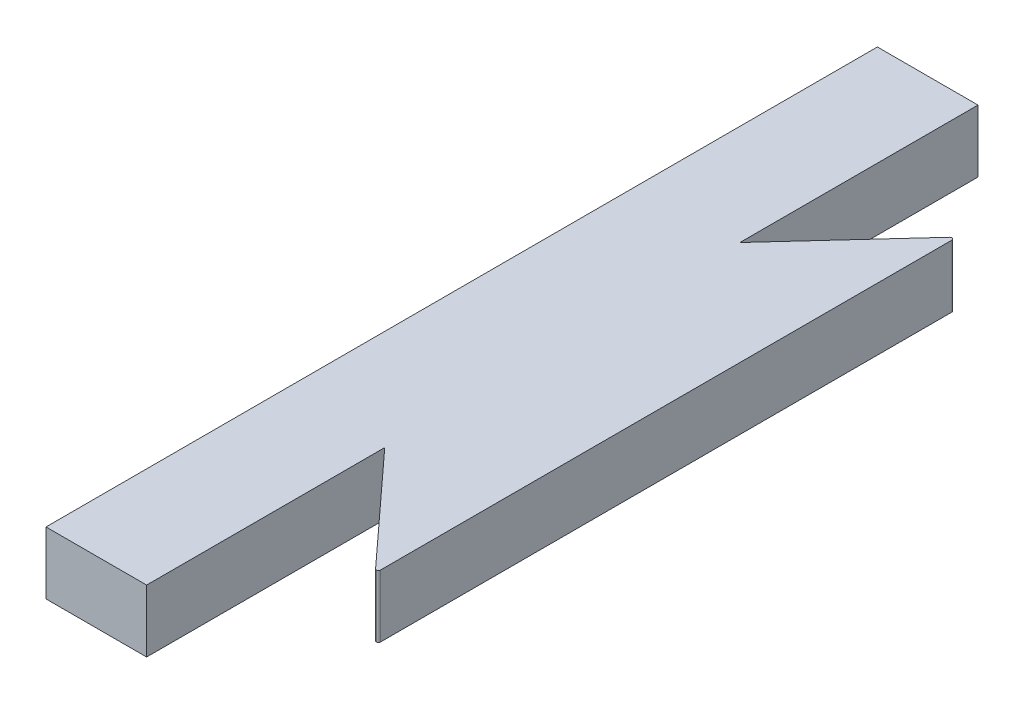
SolidWorks part; units mm, degrees
ref_plane "Alzado" through (0, 0, 0) normal (0, 0, 1) x (1, 0, 0)
ref_plane "Planta" through (0, 0, 0) normal (0, 1, 0) x (1, 0, 0)
ref_plane "Vista lateral" through (0, 0, 0) normal (1, 0, 0) x (0, 0, -1)
sketch "Croquis1" plane through (0, 0, 0) normal (0, 1, 0) x (1, 0, 0)
  line L0 (65, 8.5435) -> (70, 14)
  line L1 (-65, -20) -> (65, -20)
  line L2 (-65, -20) -> (-65, 20)
  line L3 (-65, 20) -> (65, 20)
  line L4 (65, -20) -> (65, -8.5435)
  line L5 (-65, -20) -> (65, 20) construction
  line L6 (-65, 20) -> (65, -20) construction
  line L7 (70, 14) -> (70, -14)
  line L8 (70, -14) -> (65, -8.5435)
  line L9 (65, 8.5435) -> (65, 20)
  line L10 (0, 0) -> (77.1384, 0) construction
  line L12 (10, 9.5) -> (40, 9.5)
  line L13 (10, 9.5) -> (10, 12.5)
  line L14 (10, 12.5) -> (40, 12.5)
  line L15 (40, 9.5) -> (40, 12.5)
  line L16 (10, 9.5) -> (40, 12.5) construction
  line L17 (10, 12.5) -> (40, 9.5) construction
  line L18 (10, -12.5) -> (40, -12.5)
  line L19 (10, -12.5) -> (10, -9.5)
  line L20 (10, -9.5) -> (40, -9.5)
  line L21 (40, -12.5) -> (40, -9.5)
  line L22 (10, -12.5) -> (40, -9.5) construction
  line L23 (10, -9.5) -> (40, -12.5) construction
  circle A2 centre (-50.1299, 0) radius 11
  circle A3 centre (-50.1299, 0) radius 12.5 construction
  circle A4 centre (-28.5951, 0) radius 2
  circle A5 centre (-13.5951, 0) radius 2
  circle A6 centre (50, 0) radius 2
  point P0 (0, 0)
  point P8 (70, 0)
  point P19 (25, 11)
  point P35 (25, -11)
  dimension "D8" = 22
  dimension "D12" = 25
  dimension "D13" = 4
  dimension "D14" = 4
  dimension "D17" = 4
  dimension "D1" = 130
  dimension "D2" = 5
  dimension "D3" = 42.5
  dimension "D5" = 28
  dimension "D6" = 40
  dimension "D9" = 3
  dimension "D10" = 30
  dimension "D11" = 40
  dimension "D15" = 15
  dimension "D16" = 10
  dimension "D18" = 12.5
  dimension "D19" = 12.5
extrude "Saliente-Extruir1" add sketch "Croquis1" along normal blind 3
sketch "Croquis2" plane through (0, 3, 0) normal (0, 1, 0) x (1, 0, 0)
  circle A0 centre (-50.1299, 0) radius 11
  circle A1 centre (-50.1299, 0) radius 13
  dimension "D1" = 2
extrude "Saliente-Extruir2" add sketch "Croquis2" along normal blind 4
sketch "Croquis3" plane through (0, 7, 0) normal (0, 1, 0) x (1, 0, 0)
  circle A0 centre (-50.1299, 0) radius 13
  circle A1 centre (-50.1299, 0) radius 9
  dimension "D1" = 18
extrude "Saliente-Extruir3" add sketch "Croquis3" along normal blind 2
chamfer "Chaflán1" distance 2 angle 45 1 edges at (-50.1299, 9, 13)
chamfer "Chaflán2" distance 10 angle 45 2 edges at (-65, 1.5, 20) (-65, 1.5, -20)
sketch "Croquis4" plane through (0, 3, 0) normal (0, 1, 0) x (1, 0, 0)
  line L1 (60.1587, 28.398) -> (-68.6747, 28.398)
  line L2 (60.1587, 28.398) -> (60.1587, -29.8358)
  line L3 (60.1587, -29.8358) -> (-68.6747, -29.8358)
  line L4 (-68.6747, 28.398) -> (-68.6747, -29.8358)
extrude "Cortar-Extruir1" cut sketch "Croquis4" against normal blind 10 and the other way blind 10
fillet "Redondeo1" radius 0.1 2 edges at (70, 1.5, -14) (70, 1.5, 14)
